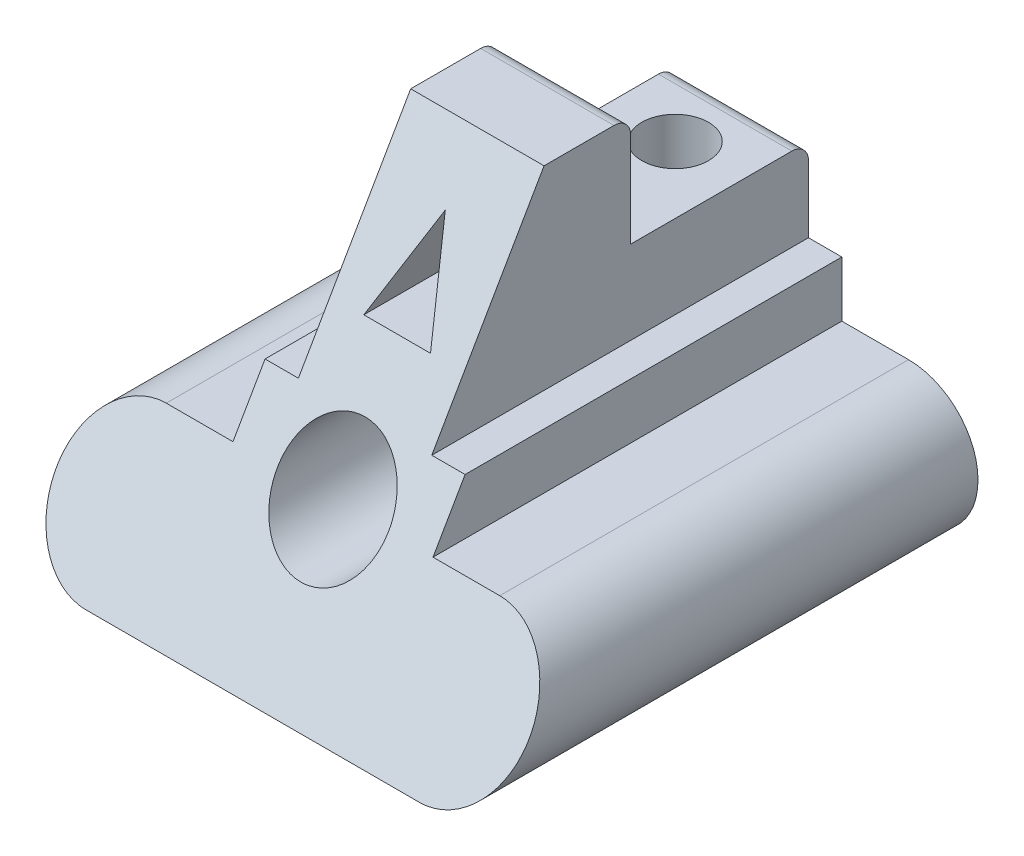
SolidWorks part; units mm, degrees
ref_plane "Plano frontal" through (0, 0, 0) normal (0, 0, 1) x (1, 0, 0)
ref_plane "Plano superior" through (0, 0, 0) normal (0, 1, 0) x (1, 0, 0)
ref_plane "Plano direito" through (0, 0, 0) normal (1, 0, 0) x (0, 0, -1)
sketch "Esboço1" plane through (0, 0, 0) normal (0, 0, 1) x (1, 0, 0)
  line L0 (-60, 25) -> (-48, 25)
  line L1 (0, 0) -> (-60, 0)
  line L2 (-48, 25) -> (-48, 35)
  line L3 (-48, 35) -> (-42, 35)
  line L4 (-42, 35) -> (-42, 50)
  line L5 (-42, 50) -> (-18, 50)
  line L6 (-18, 50) -> (-18, 35)
  line L7 (-18, 35) -> (-12, 35)
  line L8 (-12, 35) -> (-12, 25)
  line L9 (-12, 25) -> (0, 25)
  line L10 (-42, 50) -> (-42, 70)
  line L11 (-42, 70) -> (-18, 70)
  line L12 (-18, 70) -> (-18, 50)
  line L13 (-36, 45) -> (-24, 45)
  line L14 (-24, 45) -> (-30, 60)
  line L15 (-30, 60) -> (-36, 45)
  arc A0 (-60, 25) -> (-60, 0) centre (-60, 12.5) ccw
  arc A1 (0, 0) -> (0, 25) centre (0, 12.5) ccw
  circle A2 centre (-30, 25) radius 10
  point P20 (0, 0)
  point P22 (-30, 45)
  point P23 (0, 0)
  point P24 (-30, 0)
  point P25 (0, 0)
  point P26 (0, 0)
  point P28 (0, 0)
  dimension "D1" = 25
  dimension "D3" = 10
  dimension "D10" = 20
  dimension "D2" = 60
  dimension "D4" = 12
  dimension "D5" = 15
  dimension "D6" = 15
  dimension "D7" = 12
  dimension "D8" = 45
  dimension "D9" = 70
  dimension "D11" = 24
extrude "Ressalto-extrusão1" add sketch "Esboço1" against normal blind 88 contours L1 A1 L9 L8 L7 L6 L5 L14 L13 L15 L4 L3 L2 L0 A0 A2 | L5 L15 L13 L14 region at (-54, 24.0138, 0) region at (-30, 47.3333, 0)
extrude "Ressalto-extrusão2" add sketch "Esboço1<6>" against normal blind 56 contours L14 L15 L5 | L15 L14 L5 L12 L11 L10 region at (-30, 60.6061, 0) region at (-30, 53.3333, 0)
sketch "Esboço1<6>" plane through (0, 0, 0) normal (0, 0, 1) x (1, 0, 0) same geometry as "Esboço1"
sketch "Esboço2" plane through (-42, 0, 0) normal (-1, 0, 0) x (0, 0, 1)
  line L0 (-40.4145, 70) -> (0, 0)
  line L1 (-56, 70) -> (0, 70) construction
  line L4 (-40.4145, 70) -> (0, 70)
  line L5 (0, 70) -> (0, 50) construction
  line L6 (0, 70) -> (0, 0)
  dimension "D1" = 30
extrude "Corte-extrusão1" cut sketch "Esboço2" against normal up to next and the other way up to next
extrude "Corte-extrusão2" cut sketch "Esboço1<8>" against normal blind 50 contours L14 L15 L13
sketch "Esboço1<8>" plane through (0, 0, 0) normal (0, 0, 1) x (1, 0, 0) same geometry as "Esboço1"
sketch "Esboço3" plane through (0, 50, 0) normal (0, 1, 0) x (1, 0, 0)
  line L0 (-42, 88) -> (-42, 56) construction
  line L1 (-42, 88) -> (-18, 88) construction
  circle A0 centre (-30, 76) radius 6
  dimension "D1" = 12
  dimension "D2" = 12
  dimension "D3" = 12
extrude "Corte-extrusão6" cut sketch "Esboço3" against normal up to next
fillet "Filete1" radius 3 1 edges at (-30, 70, -56)
fillet "Filete2" radius 3 1 edges at (-30, 50, -88)
